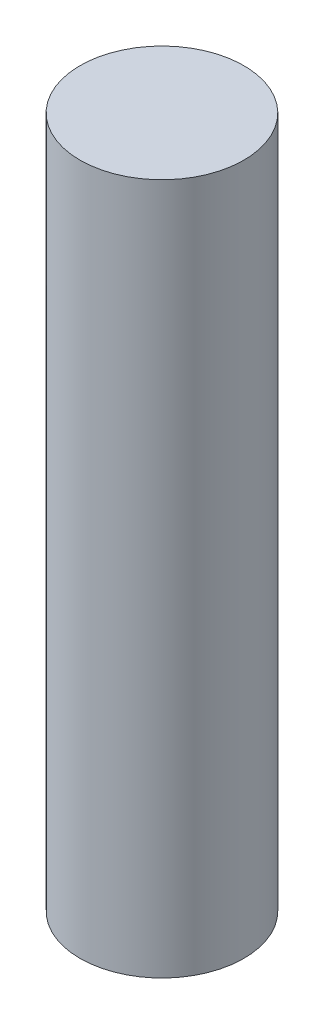
SolidWorks part; units mm, degrees
ref_plane "Front Plane" through (0, 0, 0) normal (0, 0, 1) x (1, 0, 0)
ref_plane "Top Plane" through (0, 0, 0) normal (0, 1, 0) x (1, 0, 0)
ref_plane "Right Plane" through (0, 0, 0) normal (1, 0, 0) x (0, 0, -1)
sketch "Sketch1" plane through (0, 0, 0) normal (0, 1, 0) x (1, 0, 0)
  circle A0 centre (0, 0) radius 11.85
  dimension "D1" = 23.7
extrude "Boss-Extrude1" add sketch "Sketch1" along normal blind 100
